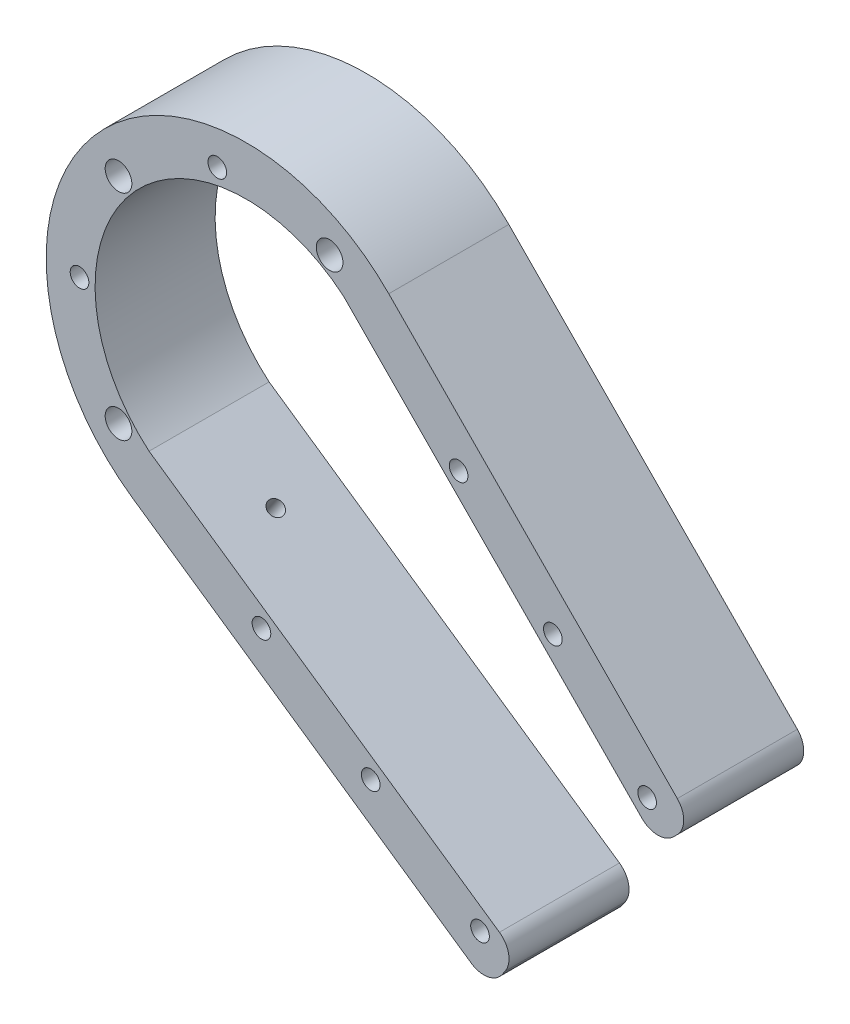
SolidWorks part; units mm, degrees
material "ABS"
ref_plane "Front Plane" through (0, 0, 0) normal (0, 0, 1) x (1, 0, 0)
ref_plane "Top Plane" through (0, 0, 0) normal (0, 1, 0) x (1, 0, 0)
ref_plane "Right Plane" through (0, 0, 0) normal (1, 0, 0) x (0, 0, -1)
sketch "Sketch1" plane through (0, 0, 10) normal (0, 0, 1) x (1, 0, 0)
  line L0 (-25.5349, -37.0536) -> (50.6196, -89.5342)
  line L1 (-25.5349, -37.0536) -> (126.1136, -141.5596) construction
  line L2 (0, 0) -> (21.8548, 26.0455) construction
  line L3 (0, 0) -> (-21.8548, -26.0455) construction
  line L4 (-21.8548, -26.0455) -> (56.948, -80.3511)
  line L5 (32.0566, 31.5812) -> (161.3084, -99.6161) construction
  line L6 (0, 0) -> (141.7182, -118.9157) construction
  line L7 (21.8548, 26.0455) -> (89.0193, -42.13)
  line L8 (32.0566, 31.5812) -> (96.964, -34.3031)
  line L9 (90.1797, -37.4944) -> (95.1302, -43.1285) construction
  line L10 (26.7138, 26.3177) -> (155.9656, -104.8796) construction
  line L11 (96.9111, -41.374) -> (96.0902, -42.1828)
  line L12 (52.5844, -82.2989) -> (58.9925, -86.1958) construction
  line L13 (-21.2791, -30.878) -> (130.3694, -135.384) construction
  line L14 (58.2278, -87.3054) -> (57.5739, -88.2543)
  arc A1 (21.8548, 26.0455) -> (-21.8548, -26.0455) centre (0, 0) ccw
  arc A3 (32.0566, 31.5812) -> (-25.5349, -37.0536) centre (0, 0) ccw
  arc A4 (32.0566, 31.5812) -> (-25.5349, -37.0536) centre (0, 0) ccw construction
  circle A5 centre (90.1797, -37.4944) radius 1.6
  circle A6 centre (68.9739, -16.2739) radius 1.6
  circle A7 centre (47.768, 4.9466) radius 1.6
  circle A8 centre (18.75, 32.476) radius 1.6
  circle A9 centre (-6.5118, 36.9303) radius 1.6
  circle A10 centre (-28.7267, 24.1045) radius 1.6
  circle A11 centre (-37.5, 0) radius 1.6
  circle A12 centre (-28.7267, -24.1045) radius 1.6
  circle A13 centre (3.4233, -47.9013) radius 1.6
  circle A14 centre (28.0039, -65.1001) radius 1.6
  circle A15 centre (52.5844, -82.2989) radius 1.6
  arc A16 (56.948, -80.3511) -> (58.2278, -87.3054) centre (54.1108, -84.4682) cw
  arc A17 (50.6196, -89.5342) -> (57.5739, -88.2543) centre (53.4568, -85.4171) ccw
  arc A18 (89.0193, -42.13) -> (96.0902, -42.1828) centre (92.5811, -38.621) ccw
  arc A19 (96.9111, -41.374) -> (96.964, -34.3031) centre (93.4021, -37.8122) ccw
  point P65 (54.7367, -92.3714)
  point P70 (100.473, -37.865)
  dimension "D1" = 68
  dimension "D4" = 3.2
  dimension "D5" = 3.2
  dimension "D6" = 3.2
  dimension "D7" = 3.2
  dimension "D8" = 3.2
  dimension "D9" = 3.2
  dimension "D10" = 3.2
  dimension "D11" = 3.2
  dimension "D12" = 3.2
  dimension "D13" = 3.2
  dimension "D14" = 3.2
  dimension "D15" = 5
  dimension "D2" = 7.5
  dimension "D3" = 7.5
  dimension "D16" = 95.7025
extrude "Boss-Extrude1" add sketch "Sketch1" along normal blind 27
sketch "Sketch2" plane through (0, 0, 37) normal (0, 0, 1) x (1, 0, 0)
  circle A0 centre (52.5844, -82.2989) radius 2.1
  circle A1 centre (28.0039, -65.1001) radius 2.1
  circle A2 centre (3.4233, -47.9013) radius 2.1
  circle A3 centre (-28.7267, -24.1045) radius 2.1
  circle A4 centre (-37.5, 0) radius 2.1
  circle A5 centre (-28.7267, 24.1045) radius 2.1
  circle A6 centre (-6.5118, 36.9303) radius 2.1
  circle A7 centre (18.75, 32.476) radius 2.1
  circle A8 centre (47.768, 4.9466) radius 2.1
  circle A9 centre (68.9739, -16.2739) radius 2.1
  circle A10 centre (90.1797, -37.4944) radius 2.1
  dimension "D1" = 4.2
  dimension "D2" = 4.2
  dimension "D3" = 4.2
  dimension "D4" = 4.2
  dimension "D5" = 4.2
  dimension "D6" = 4.2
  dimension "D7" = 4.2
  dimension "D8" = 4.2
  dimension "D9" = 4.2
  dimension "D10" = 4.2
  dimension "D11" = 4.2
extrude "Cut-Extrude1" cut sketch "Sketch2" against normal up to next
sketch "Sketch3" plane through (-25.5349, -37.0536, 0) normal (-0.5674, -0.8234, 0) x (0.8234, -0.5674, 0)
  line L0 (0, 37) -> (0, 10) construction
  line L1 (0, 23.5) -> (15, 23.5) construction
  circle A0 centre (15, 23.5) radius 3
  circle A1 centre (15, 23.5) radius 1.7
  dimension "D2" = 3.4
  dimension "D3" = 6
  dimension "D1" = 15
extrude "Cut-Extrude2" cut sketch "Sketch3" against normal up to next contours A1
extrude "Cut-Extrude3" cut sketch "Sketch3<3>" against normal blind 3
sketch "Sketch3<3>" plane through (-25.5349, -37.0536, 0) normal (-0.5674, -0.8234, 0) x (0.8234, -0.5674, 0) same geometry as "Sketch3"
sketch "Sketch4" plane through (0, 0, 37) normal (0, 0, 1) x (1, 0, 0)
  circle A0 centre (18.75, 32.476) radius 3
  circle A1 centre (-28.7267, 24.1045) radius 3
  circle A2 centre (-28.7267, -24.1045) radius 3
  circle A3 centre (-28.7267, -24.1045) radius 2.1 construction
  circle A4 centre (18.75, 32.476) radius 2.1 construction
  point P7 (-25.7848, -27.1632)
  point P8 (0, 0)
  point P9 (-20.802, -29.0047)
  point P12 (24.5852, 29.7063)
  dimension "D1" = 6
  dimension "D2" = 6
  dimension "D3" = 6
extrude "Cut-Extrude4" cut sketch "Sketch4" against normal blind 15
equation "\"thighLength\"=185"
equation "\"legLength\"=200"
equation "\"m3Thru\"=3.2"
equation "\"m4Thru\"=4.3"
equation "\"shoulder5mm\"=5.1"
equation "\"6706out\"=37.125"
equation "\"6706in\"=30"
equation "\"6904out\"=30.125"
equation "\"6904in\"=17"
equation "\"D4@Sketch1\"=\"m3Thru\""
equation "\"D5@Sketch1\"=\"m3Thru\""
equation "\"D14@Sketch1\"=\"m3Thru\""
equation "\"D13@Sketch1\"=\"m3Thru\""
equation "\"D12@Sketch1\"=\"m3Thru\""
equation "\"D11@Sketch1\"=\"m3Thru\""
equation "\"D10@Sketch1\"=\"m3Thru\""
equation "\"D9@Sketch1\"=\"m3Thru\""
equation "\"D8@Sketch1\"=\"m3Thru\""
equation "\"D7@Sketch1\"=\"m3Thru\""
equation "\"D6@Sketch1\"=\"m3Thru\""
equation "\"m3Insert\"=4.2"
equation "\"m4Insert\"=5.3"
equation "\"D1@Sketch2\"=\"m3Insert\""
equation "\"D2@Sketch2\"=\"m3Insert\""
equation "\"D3@Sketch2\"=\"m3Insert\""
equation "\"D4@Sketch2\"=\"m3Insert\""
equation "\"D5@Sketch2\"=\"m3Insert\""
equation "\"D6@Sketch2\"=\"m3Insert\""
equation "\"D7@Sketch2\"=\"m3Insert\""
equation "\"D8@Sketch2\"=\"m3Insert\""
equation "\"D9@Sketch2\"=\"m3Insert\""
equation "\"D10@Sketch2\"=\"m3Insert\""
equation "\"D11@Sketch2\"=\"m3Insert\""
